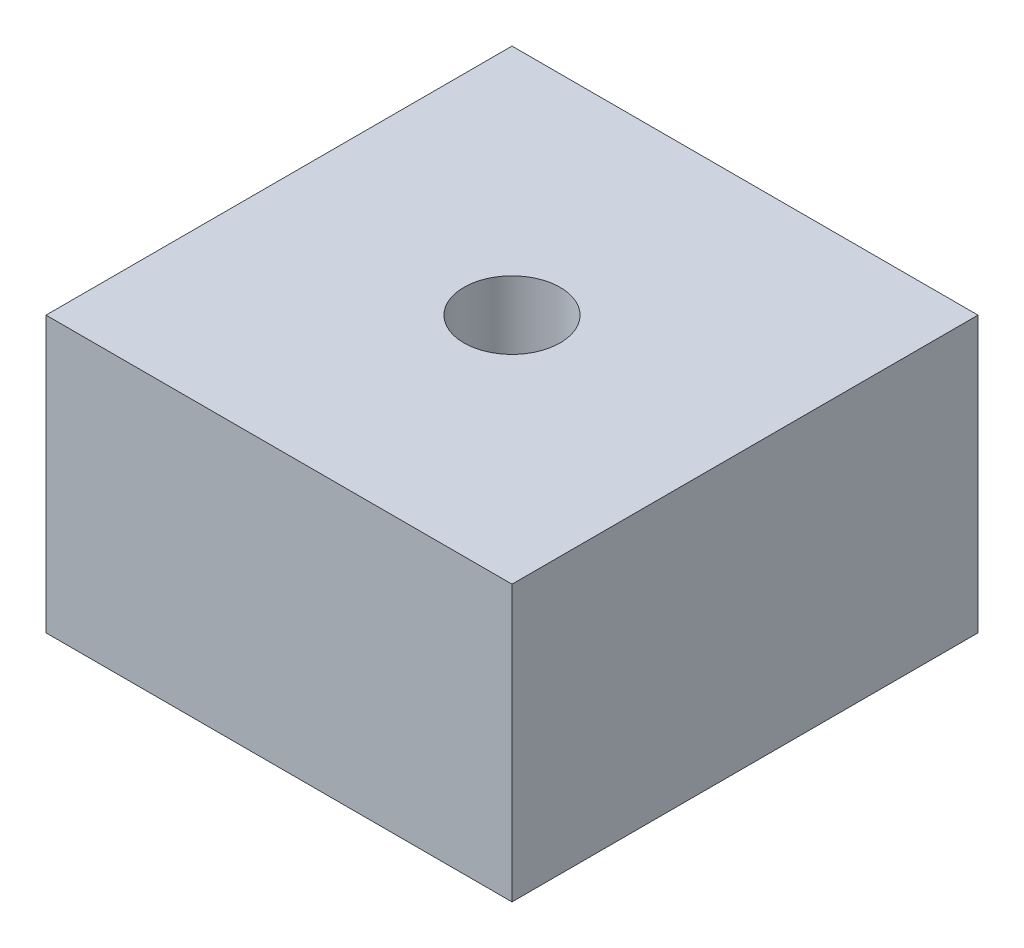
SolidWorks part; units mm, degrees
ref_plane "Front Plane" through (0, 0, 0) normal (0, 0, 1) x (1, 0, 0)
ref_plane "Top Plane" through (0, 0, 0) normal (0, 1, 0) x (1, 0, 0)
ref_plane "Right Plane" through (0, 0, 0) normal (1, 0, 0) x (0, 0, -1)
sketch "Sketch1" plane through (0, 0, 0) normal (0, 1, 0) x (1, 0, 0)
  line L1 (-25.4, 25.4) -> (25.4, 25.4)
  line L2 (-25.4, 25.4) -> (-25.4, -25.4)
  line L3 (-25.4, -25.4) -> (25.4, -25.4)
  line L4 (25.4, 25.4) -> (25.4, -25.4)
  line L5 (-25.4, 25.4) -> (25.4, -25.4) construction
  line L6 (-25.4, -25.4) -> (25.4, 25.4) construction
  circle A0 centre (0, 0) radius 5.25
  dimension "D1" = 50.8
  dimension "D2" = 50.8
extrude "Boss-Extrude1" add sketch "Sketch1" along normal blind 30
